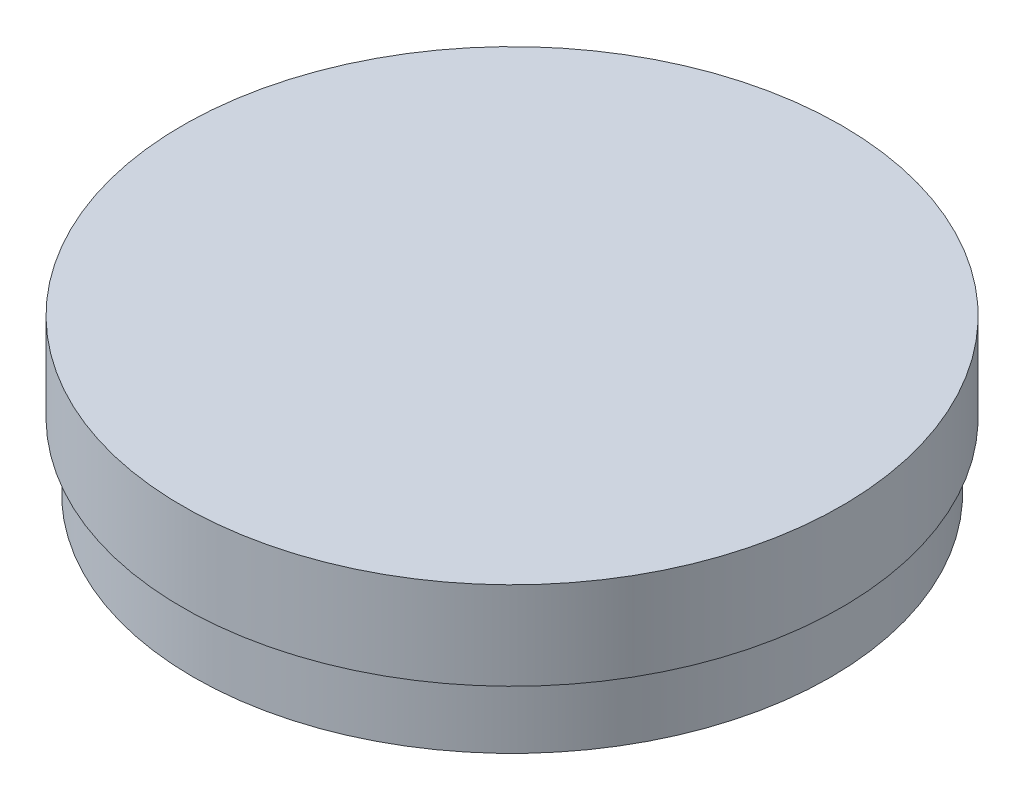
SolidWorks part; units mm, degrees
material "Polyethylene Cross-Linked"
ref_plane "Front Plane" through (0, 0, 0) normal (0, 0, 1) x (1, 0, 0)
ref_plane "Top Plane" through (0, 0, 0) normal (0, 1, 0) x (1, 0, 0)
ref_plane "Right Plane" through (0, 0, 0) normal (1, 0, 0) x (0, 0, -1)
sketch "Sketch1" plane through (0, 0, 0) normal (0, 0, 1) x (1, 0, 0)
  line L0 (0, 0) -> (0, 92.3285) construction
  line L1 (0, 0) -> (92.075, 0)
  line L2 (92.075, 0) -> (92.075, 19.05)
  line L3 (92.075, 19.05) -> (95.25, 19.05)
  line L4 (95.25, 19.05) -> (95.25, 44.45)
  line L5 (95.25, 44.45) -> (0, 44.45)
  line L6 (0, 44.45) -> (0, 0)
  dimension "D1" = 95.25
  dimension "D2" = 3.175
  dimension "D3" = 19.05
  dimension "D4" = 25.4
revolve "Revolve1" add sketch "Sketch1" angle 360 about L0
ref_plane "Plane1" through (0, 0, 101) normal (0, 0, 1) x (1, 0, 0)
ref_plane "Plane2" through (92.075, 0, 0) normal (1, 0, 0) x (0, 0, -1)
shell "Shell1" thickness 12.7 removed face at (0, 0, -92.075)
sketch "Sketch2" plane through (0, 0, 0) normal (1, 0, 0) x (0, 0, -1)
  line L0 (-42.4802, -11.43) -> (-42.4802, 11.43) construction
  line L1 (-92.075, 0) -> (92.075, 0) construction
  line L2 (-48.8302, -11.43) -> (-48.8302, 11.43)
  line L3 (-36.1302, -11.43) -> (-36.1302, 11.43)
  line L5 (21.4481, -11.43) -> (21.4481, 11.43) construction
  line L6 (15.0981, -11.43) -> (15.0981, 11.43)
  line L7 (27.7981, -11.43) -> (27.7981, 11.43)
  line L8 (-42.4802, -5.7006) -> (-42.4802, 27.8494) construction
  line L11 (21.4481, -4.583) -> (21.4481, 28.967) construction
  line L12 (-92.075, 19.05) -> (92.075, 19.05) construction
  arc A0 (-48.8302, -11.43) -> (-36.1302, -11.43) centre (-42.4802, -11.43) ccw
  arc A1 (-36.1302, 11.43) -> (-48.8302, 11.43) centre (-42.4802, 11.43) ccw
  arc A2 (15.0981, -11.43) -> (27.7981, -11.43) centre (21.4481, -11.43) ccw
  arc A3 (27.7981, 11.43) -> (15.0981, 11.43) centre (21.4481, 11.43) ccw
  point P4 (-42.4802, 0)
  point P10 (21.4481, 0)
  point P34 (-42.4802, 17.78)
  dimension "D2" = 1.27
  dimension "D1" = 12.7
  dimension "D3" = 12.7
extrude "Cut-Extrude2" [suppressed] cut sketch "Sketch2" along normal up to next
